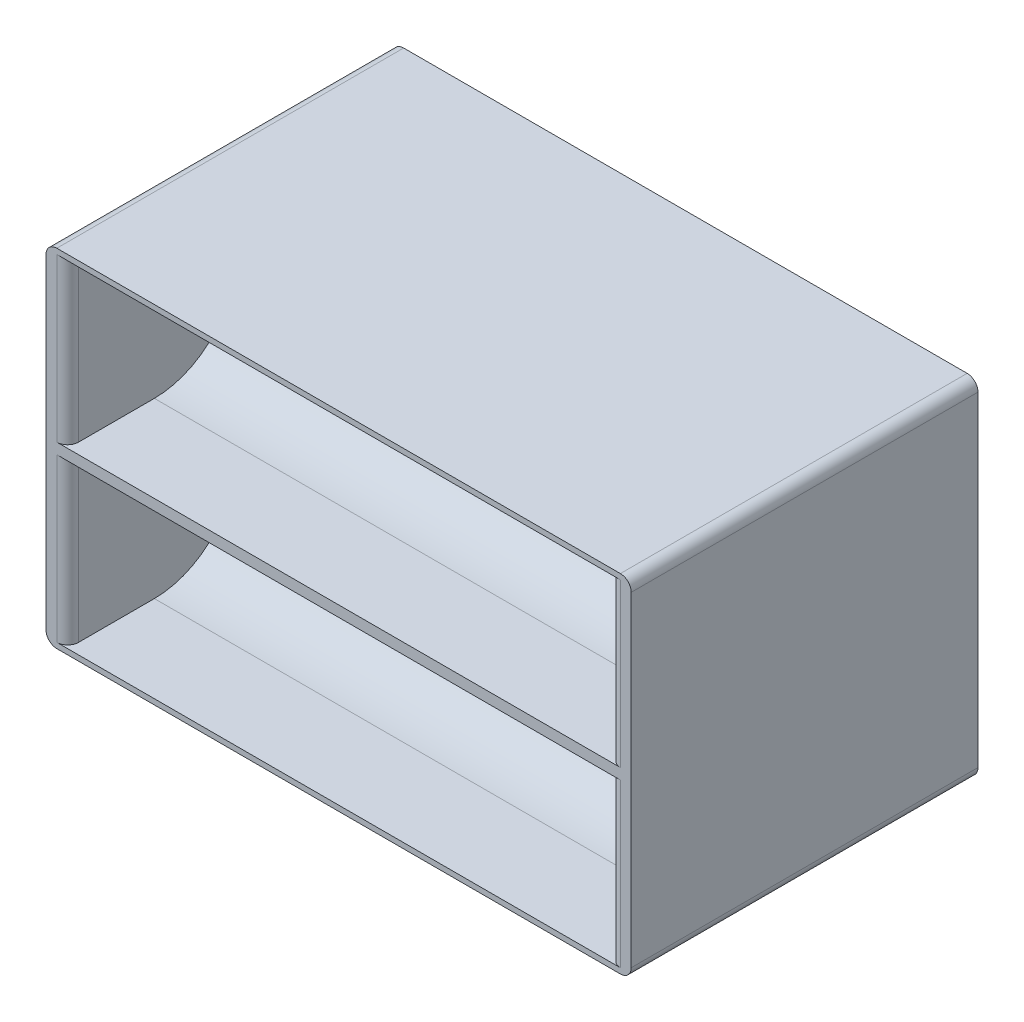
SolidWorks part; units mm, degrees
ref_plane "Front Plane" through (0, 0, 0) normal (0, 0, 1) x (1, 0, 0)
ref_plane "Top Plane" through (0, 0, 0) normal (0, 1, 0) x (1, 0, 0)
ref_plane "Right Plane" through (0, 0, 0) normal (1, 0, 0) x (0, 0, -1)
sketch "Sketch1" plane through (0, 0, 0) normal (0, 1, 0) x (1, 0, 0)
  line L1 (27, -16) -> (-27, -16)
  line L2 (27, -16) -> (27, 16)
  line L3 (27, 16) -> (-27, 16)
  line L4 (-27, -16) -> (-27, 16)
  line L5 (27, -16) -> (-27, 16) construction
  line L6 (27, 16) -> (-27, -16) construction
  point P0 (0, 0)
  dimension "D1" = 32
  dimension "D2" = 54
extrude "Boss-Extrude1" add sketch "Sketch1" along normal blind 32
sketch "Sketch2" plane through (0, 0, 0) normal (1, 0, 0) x (0, 0, -1)
  line L0 (0, 32) -> (0, 0) construction
  line L1 (-16, 32) -> (16, 32) construction
  line L2 (-16, 16) -> (16, 16) construction
  line L3 (-16, 32) -> (-16, 0) construction
  line L4 (16, 32) -> (16, 0) construction
  line L5 (-16, 32) -> (0, 32) construction
  line L6 (-8, 32) -> (-8, 31.5) construction
  line L7 (-16, 32) -> (-16, 16) construction
  line L8 (-16, 24) -> (-8, 24) construction
  line L9 (-8, 31.5) -> (-16, 31.5)
  line L10 (-16, 31.5) -> (-16, 16.5)
  line L11 (-16, 16.5) -> (-8, 16.5)
  line L12 (-8, 16.5) -> (-8, 16) construction
  line L13 (-0.5, 24) -> (0, 24) construction
  line L14 (16, 16.5) -> (8, 16.5)
  line L15 (8, 31.5) -> (16, 31.5)
  line L16 (16, 31.5) -> (16, 16.5)
  line L17 (16, 0.5) -> (16, 15.5)
  line L18 (8, 0.5) -> (16, 0.5)
  line L19 (16, 15.5) -> (8, 15.5)
  line L20 (-16, 15.5) -> (-8, 15.5)
  line L21 (-8, 0.5) -> (-16, 0.5)
  line L22 (-16, 0.5) -> (-16, 15.5)
  arc A0 (-8, 16.5) -> (-8, 31.5) centre (-8, 24) ccw
  arc A1 (8, 16.5) -> (8, 31.5) centre (8, 24) cw
  arc A2 (8, 15.5) -> (8, 0.5) centre (8, 8) ccw
  arc A3 (-8, 15.5) -> (-8, 0.5) centre (-8, 8) cw
  dimension "D1" = 15
extrude "Cut-Extrude1" cut sketch "Sketch2" against normal blind 25 and the other way blind 25
fillet "Fillet1" radius 1 12 edges at (-27, 0, 0) (27, 0, 0) (27, 32, 0) (-27, 32, 0) (25, 8, 16) (-25, 8, 16) (-25, 24, 16) (25, 24, 16) (25, 8, -16) (-25, 8, -16) (-25, 24, -16) (25, 24, -16)
